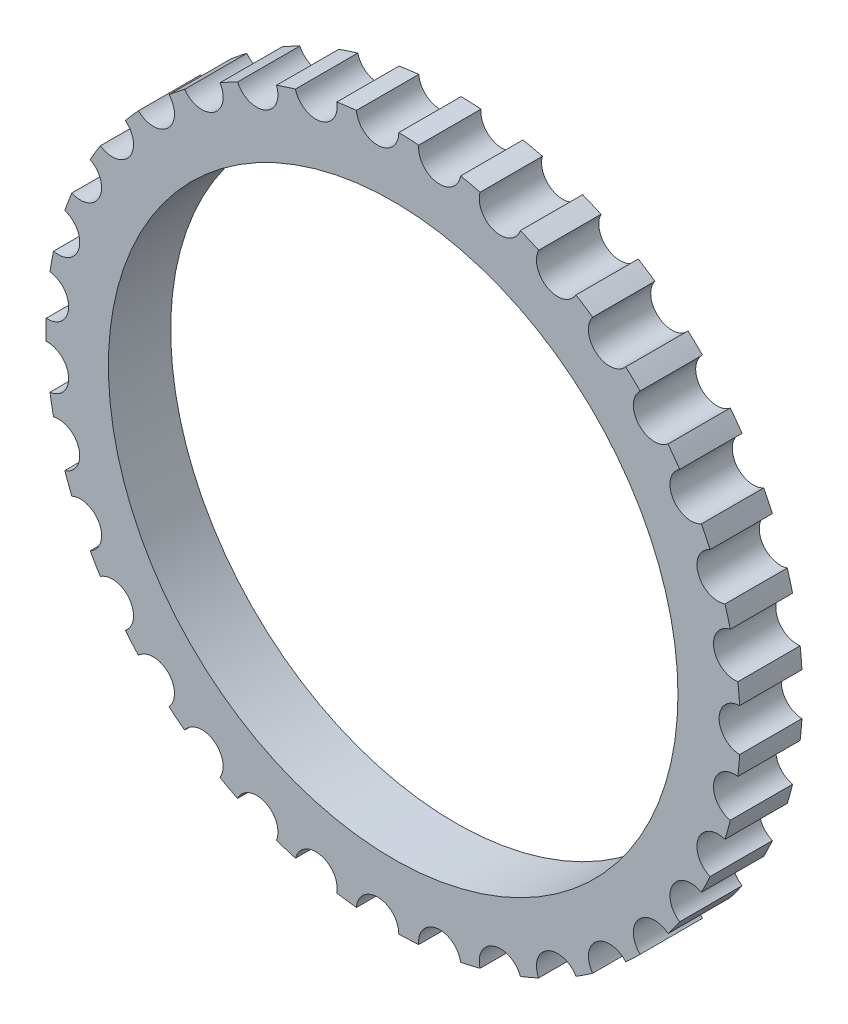
SolidWorks part; units mm, degrees
ref_plane "Front Plane" through (0, 0, 0) normal (0, 0, 1) x (1, 0, 0)
ref_plane "Top Plane" through (0, 0, 0) normal (0, 1, 0) x (1, 0, 0)
ref_plane "Right Plane" through (0, 0, 0) normal (1, 0, 0) x (0, 0, -1)
sketch "Sketch1" plane through (0, 0, 0) normal (0, 0, 1) x (1, 0, 0)
  circle A0 centre (0, 0) radius 22.8521
  circle A1 centre (0, 0) radius 27.8521
  dimension "D1" = 5
  dimension "D2" = 55.7042
extrude "Boss-Extrude1" add sketch "Sketch1" along normal blind 5
ref_plane "Plane1" through (0, 0, 2.5) normal (0, 0, 1) x (1, 0, 0)
sketch "Sketch2" plane through (0, 0, 2.5) normal (0, 0, 1) x (1, 0, 0)
  line L0 (15, 15) -> (-15, -15) construction
  line L1 (-15, -15) -> (15, -15) construction
  line L2 (-15, -15) -> (-15, 15) construction
  line L3 (-15, 15) -> (15, 15) construction
  line L4 (15, -15) -> (15, 15) construction
  circle A0 centre (-15, 15) radius 2.5
  circle A1 centre (15, 15) radius 2.5
  circle A2 centre (15, -15) radius 2.5
  circle A3 centre (-15, -15) radius 2.5
  point P4 (0, 0)
  dimension "D1" = 5
  dimension "D2" = 30
extrude "Boss-Extrude2" [suppressed] add sketch "Sketch2" along normal blind 15 and the other way blind 15
sketch "Sketch3" plane through (0, 0, 2.5) normal (0, 0, 1) x (1, 0, 0)
  circle A0 centre (0, 0) radius 27.8521 construction
  circle A1 centre (27.8521, 0) radius 1.7
  circle A2 centre (27.4045, -4.9732) radius 1.7
  circle A3 centre (26.0761, -9.7865) radius 1.7
  circle A4 centre (23.9096, -14.2853) radius 1.7
  circle A5 centre (20.9746, -18.325) radius 1.7
  circle A6 centre (17.3655, -21.7757) radius 1.7
  circle A7 centre (13.1982, -24.5264) radius 1.7
  circle A8 centre (8.6068, -26.4889) radius 1.7
  circle A9 centre (3.7387, -27.6) radius 1.7
  circle A10 centre (-1.2496, -27.8241) radius 1.7
  circle A11 centre (-6.1977, -27.1538) radius 1.7
  circle A12 centre (-10.9466, -25.6108) radius 1.7
  circle A13 centre (-15.3436, -23.2446) radius 1.7
  circle A14 centre (-19.2476, -20.1314) radius 1.7
  circle A15 centre (-22.5328, -16.3711) radius 1.7
  circle A16 centre (-25.0939, -12.0846) radius 1.7
  circle A17 centre (-26.8484, -7.4097) radius 1.7
  circle A18 centre (-27.74, -2.4966) radius 1.7
  circle A19 centre (-27.74, 2.4966) radius 1.7
  circle A20 centre (-26.8484, 7.4097) radius 1.7
  circle A21 centre (-25.0939, 12.0846) radius 1.7
  circle A22 centre (-22.5328, 16.3711) radius 1.7
  circle A23 centre (-19.2476, 20.1314) radius 1.7
  circle A24 centre (-15.3436, 23.2446) radius 1.7
  circle A25 centre (-10.9466, 25.6108) radius 1.7
  circle A26 centre (-6.1977, 27.1538) radius 1.7
  circle A27 centre (-1.2496, 27.8241) radius 1.7
  circle A28 centre (3.7387, 27.6) radius 1.7
  circle A29 centre (8.6068, 26.4889) radius 1.7
  circle A30 centre (13.1982, 24.5264) radius 1.7
  circle A31 centre (17.3655, 21.7757) radius 1.7
  circle A32 centre (20.9746, 18.325) radius 1.7
  circle A33 centre (23.9096, 14.2853) radius 1.7
  circle A34 centre (26.0761, 9.7865) radius 1.7
  circle A35 centre (27.4045, 4.9732) radius 1.7
  point P75 (0, 0)
  dimension "D1" = 55.7042
  dimension "D2" = 3.4
  dimension "D3" = 35
extrude "Cut-Extrude1" cut sketch "Sketch3" against normal mid plane 16
